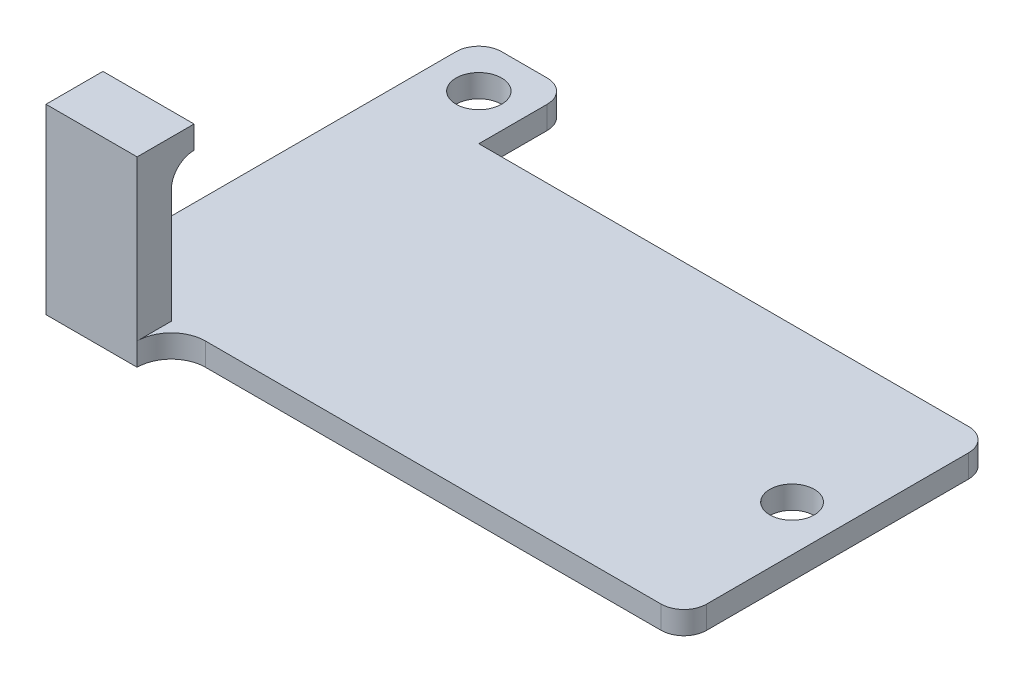
SolidWorks part; units mm, degrees
ref_plane "Plano frontal" through (0, 0, 0) normal (0, 0, 1) x (1, 0, 0)
ref_plane "Plano superior" through (0, 0, 0) normal (0, 1, 0) x (1, 0, 0)
ref_plane "Plano direito" through (0, 0, 0) normal (1, 0, 0) x (0, 0, -1)
sketch "Esboço1" plane through (0, 0, 0) normal (0, 1, 0) x (1, 0, 0)
  line L0 (-26.5, 0) -> (26.5, 0) construction
  line L1 (-26.5, 13.5) -> (26.5, 13.5)
  line L2 (-26.5, 13.5) -> (-26.5, -13.5)
  line L3 (-26.5, -13.5) -> (26.5, -13.5)
  line L4 (26.5, 13.5) -> (26.5, -13.5)
  line L5 (-26.5, 13.5) -> (26.5, -13.5) construction
  line L6 (-26.5, -13.5) -> (26.5, 13.5) construction
  line L8 (-26.5, -13.5) -> (-18.5, -13.5)
  line L9 (-26.5, -13.5) -> (-26.5, -16.5)
  line L10 (-26.5, -16.5) -> (-18.5, -16.5)
  line L11 (-18.5, -13.5) -> (-18.5, -16.5)
  line L12 (-26.5, -13.5) -> (-18.5, -16.5) construction
  line L13 (-26.5, -16.5) -> (-18.5, -13.5) construction
  line L14 (-26.5, 13.5) -> (-18.5, 13.5)
  line L15 (-26.5, 13.5) -> (-26.5, 21.5)
  line L16 (-26.5, 21.5) -> (-18.5, 21.5)
  line L17 (-18.5, 13.5) -> (-18.5, 21.5)
  line L18 (-26.5, 13.5) -> (-18.5, 21.5) construction
  line L19 (-26.5, 21.5) -> (-18.5, 13.5) construction
  circle A0 centre (-22.5, 17.5) radius 2
  point P0 (0, 0)
  point P6 (-22.5, -15)
  point P9 (0, 0)
  point P18 (-22.5, 17.5)
  dimension "D5" = 4
  dimension "D1" = 27
  dimension "D2" = 53
  dimension "D3" = 8
  dimension "D4" = 3
extrude "Ressalto-extrusão1" add sketch "Esboço1" against normal blind 2 contours L11 L3 L9 L10 | L4 L1 L2 L3 | L1 L17 L16 L15 A0 region at (-26.3869, 0, -17.5) region at (0, 0, 0) region at (-22.5, 0, 15)
sketch "Esboço2" plane through (0, 0, 0) normal (0, 1, 0) x (1, 0, 0)
  line L1 (-26.5, -16.5) -> (-18.5, -16.5)
  line L2 (-26.5, -16.5) -> (-26.5, -13.5)
  line L3 (-26.5, -13.5) -> (-18.5, -13.5)
  line L4 (-18.5, -16.5) -> (-18.5, -13.5)
  line L5 (-26.5, -16.5) -> (-18.5, -13.5) construction
  line L6 (-26.5, -13.5) -> (-18.5, -16.5) construction
  point P4 (-22.5, -15)
extrude "Ressalto-extrusão2" add sketch "Esboço2" along normal blind 14
sketch "Esboço3" plane through (0, 0, 13.5) normal (0, 0, -1) x (-1, 0, 0)
  line L0 (26.5, 14) -> (26.5, 0) construction
  line L1 (18.5, 14) -> (26.5, 14)
  line L2 (18.5, 14) -> (18.5, 12)
  line L3 (18.5, 12) -> (26.5, 12)
  line L4 (26.5, 14) -> (26.5, 12)
  line L5 (18.5, 14) -> (26.5, 12) construction
  line L6 (18.5, 12) -> (26.5, 14) construction
  point P4 (22.5, 13)
  dimension "D1" = 2
extrude "Ressalto-extrusão3" add sketch "Esboço3" along normal blind 2
fillet "Filete1" radius 2 1 edges at (-22.5, 12, 13.5)
sketch "Esboço4" plane through (0, 0, 0) normal (0, 1, 0) x (1, 0, 0)
  line L0 (0, 0) -> (26.5, 0) construction
  line L1 (26.5, 13.5) -> (26.5, -13.5) construction
  circle A0 centre (22.5, 0) radius 1.95
  circle A1 centre (-22.5, 17.5) radius 2 construction
  circle A2 centre (-22.5, 17.5) radius 2 construction
  dimension "D1" = 3.9
  dimension "D3" = 4
  dimension "D2" = 4
fillet "Filete2" radius 3 1 edges at (-18.5, -1, 13.5)
extrude "Corte-extrusão1" cut sketch "Esboço4" against normal blind 2
fillet "Filete3" radius 2 4 edges at (26.5, -1, 13.5) (26.5, -1, -13.5) (-26.5, -1, -21.5) (-18.5, -1, -21.5)
equation "\"D1@Esboço4\"=\"D3@Esboço4\""
